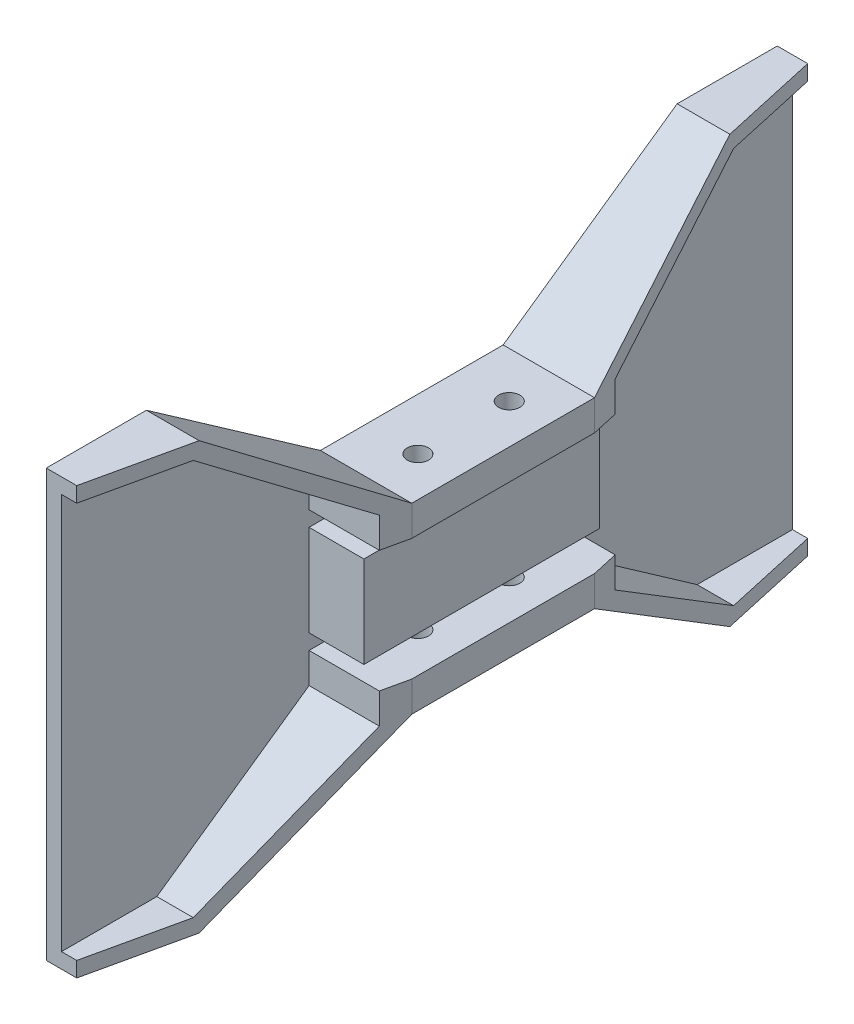
SolidWorks part; units mm, degrees
ref_plane "Front Plane" through (0, 0, 0) normal (1, 0, 0) x (0, 1, 0)
ref_plane "Top Plane" through (0, 0, 0) normal (0, 0, 1) x (0, 1, 0)
ref_plane "Right Plane" through (0, 0, 0) normal (0, 1, 0) x (-1, 0, 0)
sketch "Sketch1" plane through (0, 0, 0) normal (1, 0, 0) x (0, 1, 0)
  line L0 (-38.1, 0) -> (-38.1, -38.1)
  line L1 (0, 0) -> (-88.9, 0)
  line L2 (0, 0) -> (0, -152.4)
  line L3 (0, -152.4) -> (-88.9, -152.4)
  line L4 (-88.9, 0) -> (-88.9, -152.4)
  line L5 (-38.1, -38.1) -> (-88.9, -110.6499)
  line L6 (-82.55, -152.4) -> (-82.55, -112.6521)
  line L7 (-82.55, -112.6521) -> (-38.1, -49.1709)
  line L8 (-38.1, -49.1709) -> (-25.4, -49.1709)
  line L9 (-25.4, -49.1709) -> (-25.4, 0)
  line L10 (-19.05, 0) -> (-19.05, -49.1709)
  line L11 (-19.05, -49.1709) -> (0, -49.1709)
  dimension "D1" = 88.9
  dimension "D2" = 152.4
  dimension "D3" = 38.1
  dimension "D4" = 35
  dimension "D5" = 114.3
  dimension "D6" = 6.35
  dimension "D7" = 6.35
  dimension "D8" = 12.7
  dimension "D9" = 6.35
extrude "Boss-Extrude1" add sketch "Sketch1" against normal blind 6.35 contours L11 L10 L1 L9 L8 L7 L6 L3 L2 | L8 L9 L1 L0 L5 L4 L3 L6 L7 | L10 L11 L2 L1 region at (0, -52.9449, -64.1013) region at (0, -35.4448, -103.3686) region at (0, -9.525, -24.5854)
extrude "Boss-Extrude2" add sketch "Sketch1<4>" along normal blind 38.1 from surface contours L8 L9 L1 L0 L5 L4 L3 L6 L7 | L10 L11 L2 L1 region at (0, -52.9449, -64.1013) region at (0, -9.525, -24.5854) starting at face at (-6.35, -42.3333, -75.5917)
sketch "Sketch1<4>" plane through (0, 0, 0) normal (1, 0, 0) x (0, 1, 0) same geometry as "Sketch1"
extrude "Cut-Extrude1" cut sketch "Sketch1<6>" against normal blind 8.89 from surface contours L10 L11 L2 L1 region at (0, -9.525, -24.5854) starting at face at (31.75, -9.525, -24.5854)
sketch "Sketch1<6>" plane through (0, 0, 0) normal (1, 0, 0) x (0, 1, 0) same geometry as "Sketch1"
sketch "Sketch3" plane through (0, 0, 0) normal (0, 1, 0) x (-1, 0, 0)
  line L0 (-31.75, -49.1709) -> (0, -49.1709) construction
  line L1 (0, -112.6521) -> (0, -152.4) construction
  line L2 (0, -49.1709) -> (0, -112.6521) construction
  line L3 (-31.75, -152.4) -> (0, -152.4) construction
  line L4 (-31.75, -112.6521) -> (0, -112.6521) construction
  line L5 (-31.75, -152.4) -> (-31.75, -112.6521) construction
  line L6 (-31.75, -112.6521) -> (-31.75, -49.1709) construction
  line L7 (-31.75, -49.1709) -> (0, -49.1709)
  line L8 (0, -112.6521) -> (0, -152.4)
  line L9 (0, -49.1709) -> (0, -112.6521)
  line L10 (-31.75, -152.4) -> (0, -152.4)
  line L11 (-31.75, -112.6521) -> (0, -112.6521)
  line L12 (-31.75, -152.4) -> (-31.75, -112.6521)
  line L13 (-31.75, -112.6521) -> (-31.75, -49.1709)
  line L14 (6.35, -38.1) -> (-31.75, -38.1) construction
  line L15 (6.35, 0) -> (6.35, -152.4) construction
  line L16 (6.35, -38.1) -> (-31.75, -38.1)
  line L17 (-31.75, -38.1) -> (-31.75, -49.1709)
  line L18 (-31.75, -38.1) -> (-6.35, -152.4)
  circle A0 centre (-15.24, -19.05) radius 4.445
  dimension "D2" = 8.89
  dimension "D1" = 12.7
  dimension "D3" = 19.05
  dimension "D4" = 21.59
extrude "Cut-Extrude2" cut sketch "Sketch3" against normal through all contours L13 L11 | L11 L12 L10 | A0 | L18 L17 L7 region at (30.9299, 0, -45.4806) region at (26.1216, 0, -88.7557) region at (21.1033, 0, -133.9203) region at (15.24, 0, -19.05)
mirror "Mirror1" about plane through (-6.35, 0, 0) normal (0, -1, 0) of bodies 104
mirror "Mirror2" about plane through (-6.35, 0, 0) normal (0, 0, 1) of bodies 105
